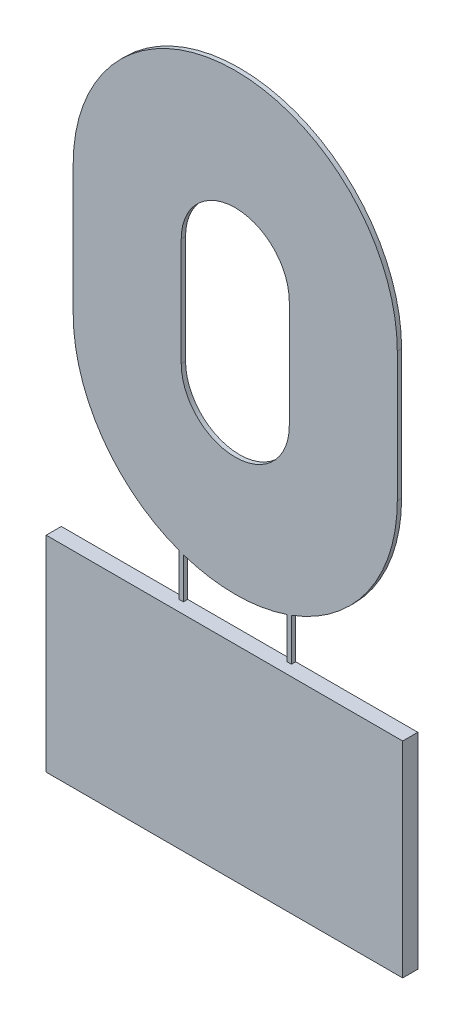
SolidWorks part; units mm, degrees
ref_plane "Front Plane" through (0, 0, 0) normal (0, 0, 1) x (1, 0, 0)
ref_plane "Top Plane" through (0, 0, 0) normal (0, 1, 0) x (1, 0, 0)
ref_plane "Right Plane" through (0, 0, 0) normal (1, 0, 0) x (0, 0, -1)
sketch "Sketch1" plane through (0, 0, 0) normal (0, 0, 1) x (1, 0, 0)
  line L0 (0, 6) -> (0, -6) construction
  line L1 (15, 6) -> (15, -6)
  line L2 (-15, 6) -> (-15, -6)
  line L3 (0, 5) -> (0, -5) construction
  line L4 (5, 5) -> (5, -5)
  line L5 (-5, 5) -> (-5, -5)
  arc A0 (15, 6) -> (-15, 6) centre (0, 6) ccw
  arc A1 (-15, -6) -> (15, -6) centre (0, -6) ccw
  arc A2 (5, 5) -> (-5, 5) centre (0, 5) ccw
  arc A3 (-5, -5) -> (5, -5) centre (0, -5) ccw
  point P2 (0, 0)
  point P8 (0, -21)
  point P9 (0, 21)
  point P12 (0, 0)
  point P17 (0, 10)
  point P18 (0, -10)
  dimension "D1" = 30
  dimension "D2" = 42
  dimension "D3" = 10
  dimension "D4" = 20
extrude "Boss-Extrude1" add sketch "Sketch1" along normal blind 0.4
sketch "Sketch2" plane through (0, 0, 0) normal (0, 0, 1) x (1, 0, 0)
  line L0 (0, -104.158) -> (0, 80.7389) construction
  line L2 (-16.5, -24) -> (16.5, -24)
  line L3 (-16.5, -24) -> (-16.5, -43)
  line L4 (-16.5, -43) -> (16.5, -43)
  line L5 (16.5, -24) -> (16.5, -43)
  line L6 (-16.5, -24) -> (16.5, -43) construction
  line L7 (-16.5, -43) -> (16.5, -24) construction
  arc A0 (-15, -6) -> (15, -6) centre (0, -6) ccw construction
  point P3 (0, -33.5)
  point P8 (0, -21)
  dimension "D1" = 19
  dimension "D2" = 33
  dimension "D3" = 3
extrude "Boss-Extrude2" add sketch "Sketch2" along normal blind 1.4 separate body
sketch "Sketch3" plane through (0, 0, 0) normal (0, 0, 1) x (1, 0, 0)
  line L0 (0, 28.9932) -> (0, -61.5176) construction
  line L2 (4.8, -18.2604) -> (5.2, -18.2604)
  line L3 (4.8, -18.2604) -> (4.8, -24.2604)
  line L4 (4.8, -24.2604) -> (5.2, -24.2604)
  line L5 (5.2, -18.2604) -> (5.2, -24.2604)
  line L6 (4.8, -18.2604) -> (5.2, -24.2604) construction
  line L7 (4.8, -24.2604) -> (5.2, -18.2604) construction
  line L8 (-5.2, -18.2212) -> (-4.8, -18.2212)
  line L9 (-5.2, -18.2212) -> (-5.2, -24.2212)
  line L10 (-5.2, -24.2212) -> (-4.8, -24.2212)
  line L11 (-4.8, -18.2212) -> (-4.8, -24.2212)
  line L12 (-5.2, -18.2212) -> (-4.8, -24.2212) construction
  line L13 (-5.2, -24.2212) -> (-4.8, -18.2212) construction
  point P3 (5, -21.2604)
  point P8 (-5, -21.2212)
  dimension "D1" = 6
  dimension "D2" = 5
  dimension "D3" = 6
  dimension "D4" = 5
  dimension "D5" = 0.4
  dimension "D6" = 0.4
extrude "Boss-Extrude3" add sketch "Sketch3" along normal up to surface (0.4 mm away) and the other way blind 0.001 up to face at (0, 0, 0.4)
